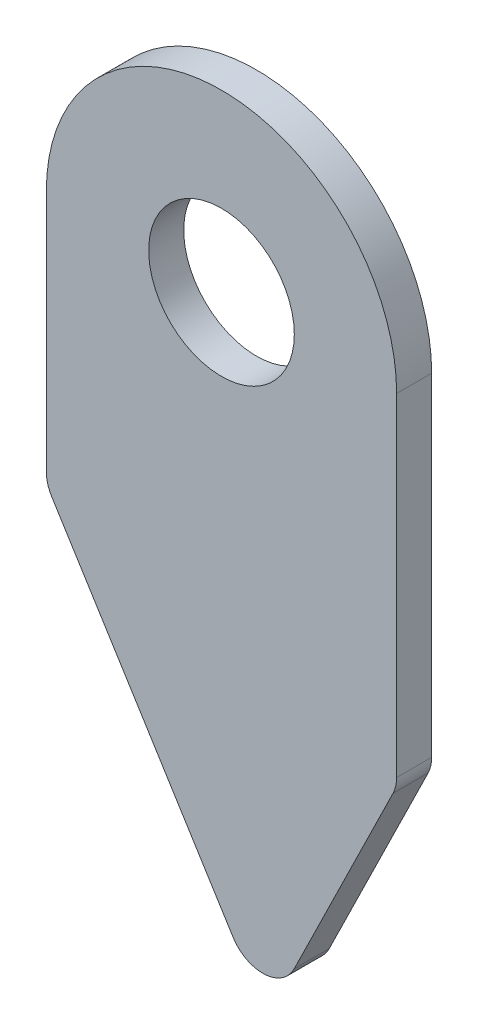
SolidWorks part; units mm, degrees
material "ASTM A36 Steel"
ref_plane "X-Y Datum" through (0, 0, 0) normal (0, 0, 1) x (1, 0, 0)
ref_plane "X-Z Datum" through (0, 0, 0) normal (0, 1, 0) x (1, 0, 0)
ref_plane "Y-Z Datum" through (0, 0, 0) normal (1, 0, 0) x (0, 0, -1)
sketch "Sketch1" plane through (0, 0, 0) normal (0, 0, 1) x (1, 0, 0)
  line L0 (-7.9375, 0) -> (-7.9375, -28.575)
  line L1 (-7.9375, -28.575) -> (7.9375, -28.575)
  line L2 (7.9375, -28.575) -> (7.9375, 0)
  circle A0 centre (0, 0) radius 7.9375
  circle A1 centre (0, 0) radius 3
  dimension "D1" = 6
  dimension "D2" = 15.875
  dimension "D3" = 28.575
extrude "Boss-Extrude1" add sketch "Sketch1" along normal blind 1.5875 contours A0 A1 | A0 L0 L1 L2 | A1 region at (0, -17.3343, 0) region at (0, 7.713, 0) region at (0, 0, 0)
hole_wizard "M6 Clearance Hole1" positions "Sketch2" profile "Sketch3" hole size "M6" standard "ANSI Metric" end condition through all
sketch "Sketch2" plane through (0, 0, 1.5875) normal (0, 0, 1) x (1, 0, 0)
  point P0 (0, 0)
sketch "Sketch3" plane through (0, 0, 1.5875) normal (1, 0, 0) x (0, -1, 0)
  line L0 (0, 0) -> (0, 1.5875)
  line L1 (0, 1.5875) -> (3.3, 1.5875)
  line L2 (3.3, 1.5875) -> (3.3, 0)
  line L5 (3.3, 0) -> (0, 0)
  line L11 (0, -6.35) -> (0, 107.95) construction
  dimension "Thru Hole Dia." = 6.6
  dimension "Thru Hole Depth" = 1.5875
sketch "Sketch4" plane through (0, 0, 1.5875) normal (0, 0, 1) x (1, 0, 0)
  line L0 (1.3788, -19.2148) -> (-109.9479, 159.3138) construction
  line L1 (1.3788, -19.2148) -> (-109.9479, 159.3138) construction
  line L2 (6.4838, -27.4013) -> (-109.9479, 159.3138) construction
  line L3 (55.1899, 89.5082) -> (-10.3661, -44.0945) construction
  line L4 (55.1899, 89.5082) -> (-10.3661, -44.0945) construction
  line L5 (5.9742, -33.7846) -> (-113.1808, 157.2978)
  line L6 (58.6569, 87.9249) -> (-6.9456, -45.7728)
  line L7 (-1.8541, -21.2308) -> (-113.1808, 157.2978) construction
  line L8 (58.6103, 87.8299) -> (-6.9456, -45.7728) construction
  line M3 (-7.9375, 0) -> (-7.9375, -28.575)
  line M4 (-7.9375, -28.575) -> (7.9375, -28.575)
  line M5 (7.9375, -28.575) -> (7.9375, 0)
  dimension "D1" = 3.81
extrude "Cut-Extrude1" cut sketch "Sketch4" against normal through all contours L5 M4 M3 | L6 M5 M4 | L5 L6 M4 region at (2.0848, -28.2063, 1.5875) region at (5.85, -24.1314, 1.5875) region at (-4.4319, -22.8349, 1.5875)
sketch "Sketch5" [suppressed] plane through (0, 0, 1.5875) normal (0, 0, 1) x (1, 0, 0)
  line L0 (-7.9375, 0) -> (-7.9375, -28.575) construction
  line L1 (7.9375, -28.575) -> (-7.9375, -28.575)
  line L2 (7.9375, -28.575) -> (7.9375, -22.225)
  line L3 (7.9375, -22.225) -> (-7.9375, -22.225)
  line L4 (-7.9375, -28.575) -> (-7.9375, -22.225)
  dimension "D1" = 6.35
extrude "Cut-Extrude2" [suppressed] cut sketch "Sketch5" against normal through all
sketch "Sketch6" [suppressed] plane through (0, 0, 0) normal (0, 0, -1) x (-1, 0, 0)
  spline S0 degree 3 poles (11.1636, -26.4867) (3.0884, -2.4046) (-38.3742, -16.3077) (-30.299, -40.3899) (-22.2238, -64.4721) (19.2388, -50.5689) (11.1636, -26.4867) (3.0884, -2.4046) (-38.3742, -16.3077) knots -0.5 0 0 0 0.5 0.5 0.5 1 1 1 1.5 1.5 1.5 weights 1 0.333333 0.333333 1 0.333333 0.333333 1 0.333333 0.333333 only from (11.1636, -26.4867) to (11.1636, -26.4867)
  spline S1 degree 3 poles (11.1636, -26.4867) (3.0884, -2.4046) (-38.3742, -16.3077) (-30.299, -40.3899) (-22.2238, -64.4721) (19.2388, -50.5689) (11.1636, -26.4867) (3.0884, -2.4046) (-38.3742, -16.3077) knots -0.5 0 0 0 0.5 0.5 0.5 1 1 1 1.5 1.5 1.5 weights 1 0.333333 0.333333 1 0.333333 0.333333 1 0.333333 0.333333 only from (11.1636, -26.4867) to (11.1636, -26.4867)
extrude "Cut-Extrude3" [suppressed] cut sketch "Sketch6" against normal through all
fillet "Fillet1" radius 1.5875 3 edges at (7.9375, -15.441, 0.7937) (-7.9375, -11.4752, 0.7937) (2.0357, -27.4688, 0.7937)
fillet "Fillet2" [suppressed] radius 1.5875
fillet "Fillet3" [suppressed] radius 1.5875
